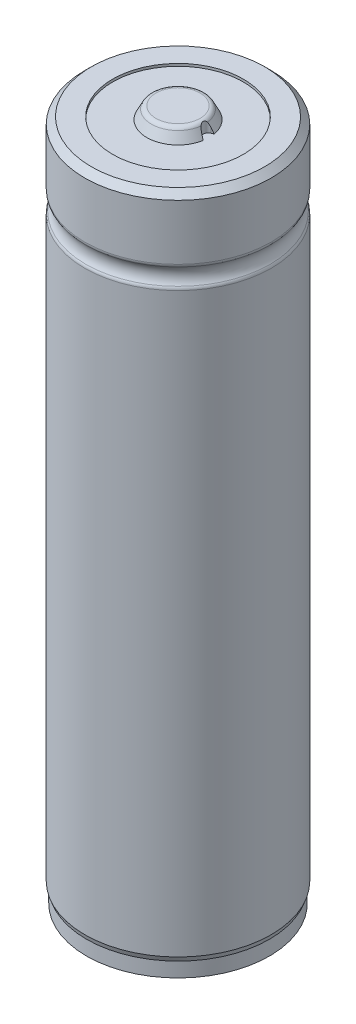
SolidWorks part; units mm, degrees
ref_plane "Ebene vorne" through (0, 0, 0) normal (0, 0, 1) x (1, 0, 0)
ref_plane "Ebene oben" through (0, 0, 0) normal (0, 1, 0) x (1, 0, 0)
ref_plane "Ebene rechts" through (0, 0, 0) normal (1, 0, 0) x (0, 0, -1)
sketch "Sketch1" plane through (0, 0, 0) normal (0, 0, 1) x (1, 0, 0)
  line L0 (0, 93.4228) -> (0, -25.6515) construction
  line L1 (0, -55) -> (0, 55) construction
  line L2 (0, 68.75) -> (-2.5, 68.75)
  line L3 (-6.5, 67.8) -> (-6.5, 67.55)
  line L4 (-6.5, 67.55) -> (-3.1, 67.55)
  line L5 (-2.5, 68.75) -> (-3.1, 67.55)
  line L10 (-6.5, 67.8) -> (-8.625, 67.8)
  line L11 (-8.625, 67.8) -> (-9.275, 67.15)
  line L12 (-9.275, 67.15) -> (-9.275, 61.45)
  line L13 (-7, 0) -> (-9.1, 0)
  line L14 (-9.1, 0) -> (-9.1, 2)
  line L15 (-9.275, 59.55) -> (-9.275, 2)
  line L16 (-9.1, 2) -> (-9.275, 2)
  line L17 (-7, 0) -> (-7, 0.25)
  line L18 (-7, 0.25) -> (0, 0.25)
  line L19 (0, 0.25) -> (0, 68.75)
  line L25 (0, 0) -> (-7, 0) construction
  arc A0 (-9.275, 61.45) -> (-9.275, 59.55) centre (-10.2908, 60.5) cw
  point P28 (-8.9, 60.5)
  dimension "D5" = 17.8
  dimension "D2" = 0.25
  dimension "D3" = 14
  dimension "D4" = 18.55
  dimension "D6" = 1.9
  dimension "D7" = 45
  dimension "D8" = 0.65
  dimension "D9" = 67.8
  dimension "D10" = 0.25
  dimension "D11" = 13
  dimension "D12" = 5
  dimension "D13" = 6.2
  dimension "D14" = 1.2
  dimension "D16" = 18.2
  dimension "D17" = 60.5
  dimension "D21" = 2
revolve "Revolve1" add sketch "Sketch1" angle 360 about L0
chamfer "Фаска1" distance 0.2 angle 70 1 edges at (0, 2, 9.1) first distance on face at (0, 2, 9.1)
fillet "Скругление1" radius 0.5 3 edges at (0, 59.55, 9.275) (0, 61.45, 9.275) (0, 68.75, 2.5)
sketch "Эскиз1" plane through (0, 68.75, 0) normal (0, 1, 0) x (1, 0, 0)
  line L0 (-2.8301, -0.4702) -> (-3.0508, -0.55)
  line L1 (-2.8301, 0.4702) -> (-3.0508, 0.55)
  line L3 (0, -10.2025) -> (0, 10.2025) construction
  line L4 (2.8301, 0.4702) -> (3.0508, 0.55)
  line L5 (2.8301, -0.4702) -> (3.0508, -0.55)
  arc A1 (-2.8301, -0.4702) -> (-2.8301, 0.4702) centre (-3, 0) ccw
  arc A2 (-3.0508, 0.55) -> (-3.0508, -0.55) centre (0, 0) ccw
  circle A3 centre (0, 0) radius 2.5 construction
  arc A4 (3.0508, 0.55) -> (3.0508, -0.55) centre (0, 0) cw
  circle A5 centre (0, 0) radius 3.1 construction
  arc A6 (2.8301, -0.4702) -> (2.8301, 0.4702) centre (3, 0) cw
  point P8 (-2.6329, 0)
  point P10 (-3.1876, -0.8813)
  point P12 (-3.0724, 0.4129)
  point P13 (-2.6169, -0.112)
  point P14 (-2.4346, -0.5679)
  point P15 (-2.4634, -0.4265)
  point P16 (-2.5332, 0)
  point P17 (-2.5685, 0.1182)
  point P18 (0, 0)
  point P20 (-2.9575, -0.503)
  point P21 (0, 0)
  point P22 (-2.999, 0.0792)
  point P23 (-2.9863, 0.2796)
  point P24 (0, 0)
  point P27 (0, 0)
  dimension "D1" = 1.1
  dimension "D2" = 0.5
extrude "Вырез-Вытянуть1" cut sketch "Эскиз1" against normal up to surface (1.2 mm away) up to face at (0, 67.55, 6.5)
